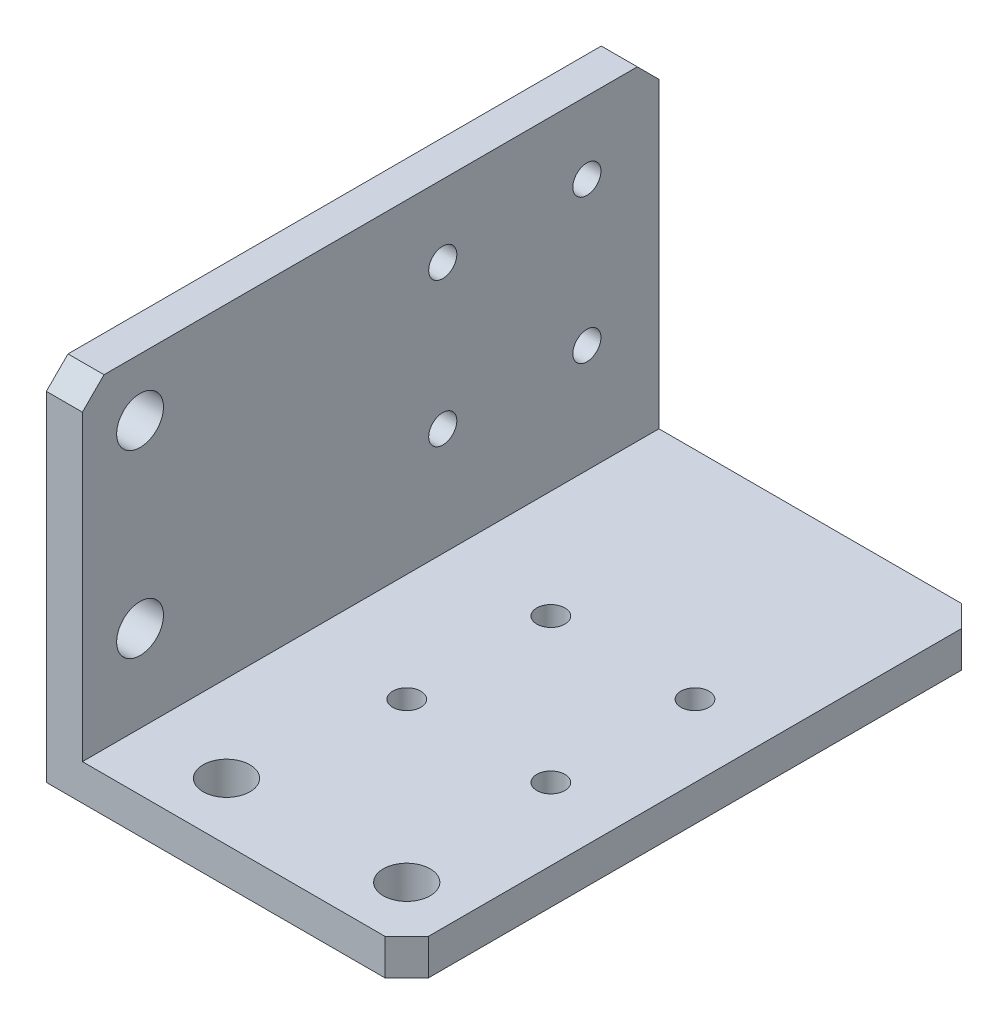
SolidWorks part; units mm, degrees
material "Lega 1060"
ref_plane "Piano frontale" through (0, 0, 0) normal (0, 0, 1) x (1, 0, 0)
ref_plane "Piano superiore" through (0, 0, 0) normal (0, 1, 0) x (1, 0, 0)
ref_plane "Piano destro" through (0, 0, 0) normal (1, 0, 0) x (0, 0, -1)
sketch "Schizzo1" plane through (0, 0, 0) normal (0, 0, 1) x (1, 0, 0)
  line L0 (0, 0) -> (0, 50)
  line L1 (0, 50) -> (5, 50)
  line L2 (5, 50) -> (5, 5)
  line L3 (5, 5) -> (50, 5)
  line L4 (50, 5) -> (50, 0)
  line L5 (50, 0) -> (0, 0)
  dimension "D1" = 5
  dimension "D2" = 5
  dimension "D3" = 50
  dimension "D4" = 50
extrude "Estrusione-Estrusione1" add sketch "Schizzo1" along normal blind 80
sketch "Schizzo2" plane through (0, 0, 0) normal (0, -1, 0) x (1, 0, 0)
  line L0 (5.4524, 72) -> (42.7933, 72) construction
  line L1 (0, 80) -> (50, 80) construction
  line L5 (50, 80) -> (50, 0) construction
  point P4 (17, 72)
  point P5 (42, 72)
  dimension "D1" = 8
  dimension "D2" = 25
  dimension "D3" = 8
sketch "Schizzo3" plane through (0, 0, 0) normal (-1, 0, 0) x (0, 0, 1)
  line L0 (72, 44.621) -> (72, 5.772) construction
  line L1 (80, 50) -> (80, 0) construction
  line L2 (80, 50) -> (0, 50) construction
  point P4 (72, 42)
  point P5 (72, 17)
  dimension "D1" = 8
  dimension "D2" = 8
  dimension "D3" = 25
hole_wizard "Foro Ø6.5 (6.5)-1" positions "Schizzo5" profile "Schizzo4" hole size "Ø6.5" standard "ISO" end condition through all
sketch "Schizzo5" plane through (0, 0, 0) normal (0, -1, 0) x (-1, 0, 0)
  point P0 (-17, -72)
  point P3 (-42, -72)
sketch "Schizzo4" plane through (17, 0, 72) normal (1, 0, 0) x (0, 0, -1)
  line L0 (0, 0) -> (0, 50)
  line L1 (0, 50) -> (3.25, 50)
  line L2 (3.25, 50) -> (3.25, 0)
  line L5 (3.25, 0) -> (0, 0)
  line L11 (0, -6.35) -> (0, 107.95) construction
  dimension "Thru Hole Dia." = 6.5
  dimension "Thru Hole Depth" = 50
hole_wizard "Foro Ø6.5 (6.5)-2" positions "Schizzo7" profile "Schizzo6" hole size "Ø6.5" standard "ISO"
sketch "Schizzo7" plane through (0, 0, 0) normal (-1, 0, 0) x (0, 0, 1)
  point P1 (72, 42)
  point P4 (72, 17)
sketch "Schizzo6" plane through (0, 42, 72) normal (0, 1, 0) x (0, 0, 1)
  line L0 (0, 0) -> (0, 6.9528)
  line L1 (0, 6.9528) -> (3.25, 5)
  line L2 (3.25, 5) -> (3.25, 0)
  line L5 (3.25, 0) -> (0, 0)
  line L10 (0, 6.9528) -> (-3.25, 5) construction
  line L11 (0, -6.35) -> (0, 107.95) construction
  dimension "Hole Dia." = 6.5
  dimension "Hole Depth" = 5
  dimension "Drill Angle" = 118
ref_plane "Piano1" through (0, 0, 40) normal (0, 0, 1) x (1, 0, 0)
sketch "Schizzo8" plane through (0, 0, 0) normal (-1, 0, 0) x (0, 0, 1)
  line L2 (80, 50) -> (80, 0) construction
  line L3 (80, 50) -> (0, 50) construction
  circle A0 centre (20, 30) radius 7
  dimension "D3" = 14
  dimension "D1" = 60
  dimension "D2" = 20
sketch "Schizzo9" plane through (0, 0, 0) normal (0, -1, 0) x (1, 0, 0)
  line L0 (50, 80) -> (50, 0) construction
  line L1 (0, 80) -> (50, 80) construction
  circle A0 centre (30, 40) radius 7
  dimension "D1" = 14
  dimension "D2" = 20
  dimension "D3" = 40
sketch "Schizzo10" plane through (0, 0, 0) normal (-1, 0, 0) x (0, 0, 1)
  line L1 (20, 42.2663) -> (20, 14.8621) construction
  line L2 (19.1906, 30.8094) -> (20, 30) construction
  circle A0 centre (10, 40) radius 1.75
  circle A1 centre (30, 40) radius 1.75
  circle A3 centre (30, 20) radius 1.75
  circle A4 centre (10, 20) radius 1.75
  circle A5 centre (20, 30) radius 7 construction
  point P20 (20, 30)
  dimension "D1" = 3.5
  dimension "D2" = 20
  dimension "D3" = 45
  dimension "D4" = 4
sketch "Schizzo11" plane through (0, 0, 0) normal (0, -1, 0) x (1, 0, 0)
  line L0 (30, 40) -> (14.4837, 40) construction
  line L1 (30, 40) -> (34.5929, 44.5929) construction
  circle A0 centre (20, 30) radius 1.75
  circle A3 centre (20, 50) radius 1.75
  circle A4 centre (40, 50) radius 1.75
  circle A5 centre (40, 30) radius 1.75
  circle A6 centre (30, 40) radius 7 construction
  point P2 (30, 40)
  point P17 (30, 40)
  dimension "D2" = 3.5
  dimension "D1" = 20
  dimension "D3" = 45
  dimension "D4" = 4
chamfer "Smusso1" distance 3 angle 45 4 edges at (2.5, 50, 0) (50, 2.5, 0) (2.5, 50, 80) (50, 2.5, 80)
hole_wizard "M3.5 Clearance Hole1" positions "3DSketch2" profile "Sketch2" hole size "M3.5" standard "ISO" end condition through all
sketch3d "3DSketch2"
  point P0 (0, 40, 10)
  point P3 (0, 40, 30)
  point P6 (0, 20, 30)
  point P9 (0, 20, 10)
sketch "Sketch2" plane through (0, 40, 10) normal (0, 1, 0) x (0, 0, 1)
  line L0 (0, 0) -> (0, 50)
  line L1 (0, 50) -> (1.95, 50)
  line L2 (1.95, 50) -> (1.95, 0)
  line L5 (1.95, 0) -> (0, 0)
  line L11 (0, -6.35) -> (0, 107.95) construction
  dimension "Thru Hole Dia." = 3.9
  dimension "Thru Hole Depth" = 50
hole_wizard "M3.5 Clearance Hole2" positions "3DSketch3" profile "Sketch3" hole size "M3.5" standard "ISO" end condition through all
sketch3d "3DSketch3"
  point P0 (20, 0, 50)
  point P3 (40, 0, 50)
  point P6 (40, 0, 30)
  point P9 (20, 0, 30)
sketch "Sketch3" plane through (20, 0, 50) normal (1, 0, 0) x (0, 0, -1)
  line L0 (0, 0) -> (0, 50)
  line L1 (0, 50) -> (1.95, 50)
  line L2 (1.95, 50) -> (1.95, 0)
  line L5 (1.95, 0) -> (0, 0)
  line L11 (0, -6.35) -> (0, 107.95) construction
  dimension "Thru Hole Dia." = 3.9
  dimension "Thru Hole Depth" = 50
sketch "Sketch6" plane through (0, 0, 0) normal (0, -1, 0) x (1, 0, 0)
  line L0 (0, 80) -> (47, 80) construction
  line L1 (0, 80) -> (0, 0) construction
  point P0 (5, 80)
  dimension "D1" = 5
